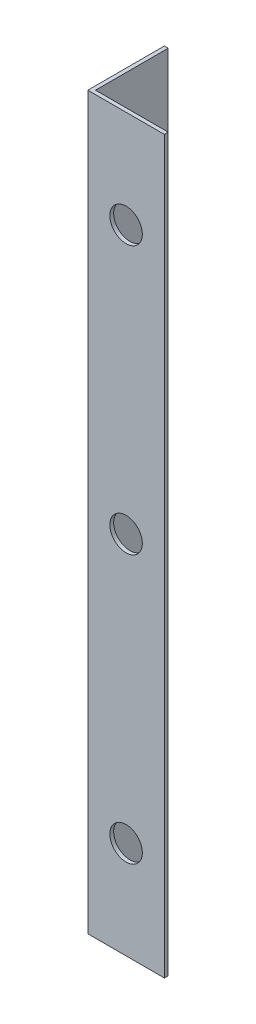
SolidWorks part; units mm, degrees
material "1060 Сплав"
ref_plane "Спереди" through (0, 0, 0) normal (0, 0, 1) x (1, 0, 0)
ref_plane "Сверху" through (0, 0, 0) normal (0, 1, 0) x (1, 0, 0)
ref_plane "Справа" through (0, 0, 0) normal (1, 0, 0) x (0, 0, -1)
sketch "Эскиз1" plane through (0, 0, 0) normal (0, 1, 0) x (1, 0, 0)
  line L0 (0, 0) -> (0, 20)
  line L1 (0, 20) -> (1, 20)
  line L2 (1, 20) -> (1, 1)
  line L3 (1, 1) -> (20, 1)
  line L4 (20, 1) -> (20, 0)
  line L5 (20, 0) -> (0, 0)
  dimension "D1" = 1
  dimension "D2" = 20
extrude "Бобышка-Вытянуть1" add sketch "Эскиз1" along normal blind 191
sketch "Эскиз2" plane through (0, 0, 0) normal (0, 0, 1) x (1, 0, 0)
  line L0 (10, 191) -> (10, 0) construction
  line L1 (0, 191) -> (20, 191) construction
  line L2 (0, 0) -> (20, 0) construction
  line L3 (20, 95.5) -> (0, 95.5) construction
  line L4 (20, 191) -> (20, 0) construction
  line L5 (0, 191) -> (0, 0) construction
  circle A1 centre (10, 165.5) radius 4.25
  circle A2 centre (10, 95.5) radius 4.25
  circle A3 centre (10, 25.5) radius 4.25
  dimension "D1" = 70
  dimension "D2" = 70
  dimension "D4" = 8.5
extrude "Вырез-Вытянуть1" cut sketch "Эскиз2" against normal through all
